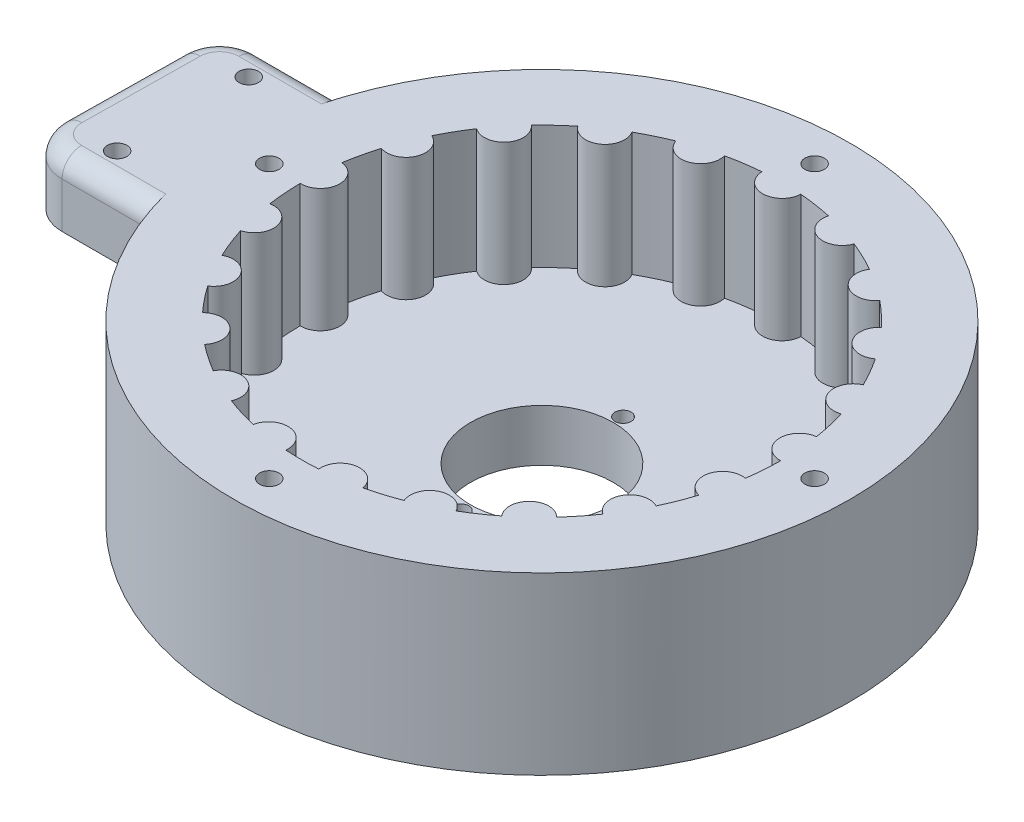
SolidWorks part; units mm, degrees
ref_plane "Front Plane" through (0, 0, 0) normal (0, 0, 1) x (1, 0, 0)
ref_plane "Top Plane" through (0, 0, 0) normal (0, 1, 0) x (1, 0, 0)
ref_plane "Right Plane" through (0, 0, 0) normal (1, 0, 0) x (0, 0, -1)
sketch "Sketch1" plane through (0, 0, 0) normal (0, 1, 0) x (1, 0, 0)
  circle A0 centre (0, 0) radius 37
  circle A1 centre (0, 37) radius 3
  circle A2 centre (10.9059, 35.3562) radius 3
  circle A3 centre (20.8428, 30.5708) radius 3
  circle A4 centre (28.9278, 23.0691) radius 3
  circle A5 centre (34.4423, 13.5176) radius 3
  circle A6 centre (36.8965, 2.765) radius 3
  circle A7 centre (36.0723, -8.2333) radius 3
  circle A8 centre (32.0429, -18.5) radius 3
  circle A9 centre (25.1664, -27.1229) radius 3
  circle A10 centre (16.0537, -33.3358) radius 3
  circle A11 centre (5.5146, -36.5867) radius 3
  circle A12 centre (-5.5146, -36.5867) radius 3
  circle A13 centre (-16.0537, -33.3358) radius 3
  circle A14 centre (-25.1664, -27.1229) radius 3
  circle A15 centre (-32.0429, -18.5) radius 3
  circle A16 centre (-36.0723, -8.2333) radius 3
  circle A17 centre (-36.8965, 2.765) radius 3
  circle A18 centre (-34.4423, 13.5176) radius 3
  circle A19 centre (-28.9278, 23.0691) radius 3
  circle A20 centre (-20.8428, 30.5708) radius 3
  circle A21 centre (-10.9059, 35.3562) radius 3
  circle A27 centre (0, 0) radius 47.5
  point P57 (0, 0)
  point P97 (0, 0)
  dimension "D1" = 74
  dimension "D2" = 21
  dimension "D3" = 95
extrude "Boss-Extrude1" add sketch "Sketch1" along normal blind 27 contours A27 A0 A1 A2 A3 A4 A5 A6 A7 A8 A9 A10 A11 A12 A13 A14 A15 A16 A17 A18 A19 A20 A21 | A13 | A12 | A14 | A15 | A16 | A17 | A18 | A19 | A20 | A21 | A1 | A2 | A3 | A4 | A5 | A6 | A7 | A8 | A9 | A10 | A11 region at (-46.1565, 0, 0)
sketch "Sketch2" plane through (0, 0, 0) normal (0, -1, 0) x (1, 0, 0)
  circle A0 centre (0, 0) radius 38
  circle A1 centre (0, 0) radius 11
  dimension "D1" = 76
  dimension "D2" = 22
extrude "Boss-Extrude2" add sketch "Sketch2" against normal blind 8
sketch "Sketch4" plane through (0, 8, 0) normal (0, 1, 0) x (1, 0, 0)
  line L0 (-11, 0) -> (11, 0) construction
  circle A0 centre (0, 12.5) radius 1.25
  circle A1 centre (0, 0) radius 11 construction
  circle A2 centre (0, -12.5) radius 1.25
  dimension "D1" = 12.5
extrude "Cut-Extrude1" cut sketch "Sketch4" against normal through all contours A2 | A0
sketch "Sketch5" plane through (0, 27, 0) normal (0, 1, 0) x (1, 0, 0)
  circle A0 centre (0, 42) radius 1.5
  circle A1 centre (42, 0) radius 1.5
  circle A2 centre (0, -42) radius 1.5
  circle A3 centre (-42, 0) radius 1.5
  point P12 (0, 0)
  dimension "D1" = 42
  dimension "D3" = 3
  dimension "D2" = 4
extrude "Cut-Extrude2" cut sketch "Sketch5" against normal blind 10 contours A0 | A3 | A2 | A1
ref_plane "Plane1" through (0, 27, 0) normal (0, 1, 0) x (1, 0, 0)
sketch "Sketch9" plane through (0, 27, 0) normal (0, 1, 0) x (1, 0, 0)
  line L0 (-43.5, 0) -> (-43.5, 15)
  line L1 (-43.5, 15) -> (-64.5942, 15)
  line L3 (-64.5942, 15) -> (-65, -15)
  line L4 (-65, -15) -> (-43.5, -15)
  line L5 (-43.5, -15) -> (-43.5, 0)
  circle A0 centre (-42, 0) radius 1.5 construction
  circle A1 centre (-42, 0) radius 1.5 construction
  dimension "D1" = 15
  dimension "D2" = 21.5
extrude "Boss-Extrude3" add sketch "Sketch9" against normal blind 10 contours L4 L5 L0 L1 L3
sketch "Sketch10" plane through (0, 27, 0) normal (0, 1, 0) x (1, 0, 0)
  line L0 (-65, -15) -> (-45.0694, -15) construction
  line L1 (-45.0694, 15) -> (-64.5942, 15) construction
  line L2 (-64.5942, 15) -> (-65, -15) construction
  circle A0 centre (-55.161, 10) radius 1.5
  circle A1 centre (-55.4315, -10) radius 1.5
  dimension "D1" = 5
  dimension "D5" = 3
  dimension "D6" = 3
  dimension "D2" = 5
  dimension "D3" = 9.5
  dimension "D4" = 9.5
extrude "Cut-Extrude3" cut sketch "Sketch10" against normal blind 10
fillet "Fillet2" radius 3 3 edges at (-54.8318, 27, -15) (-64.7971, 27, 0) (-55.0347, 27, 15)
fillet "Fillet3" radius 6 4 edges at (-64.1094, 26.1213, 14.1213) (-63.7273, 26.1213, -14.1213) (-64.5942, 20.5, -15) (-65, 20.5, 15)
